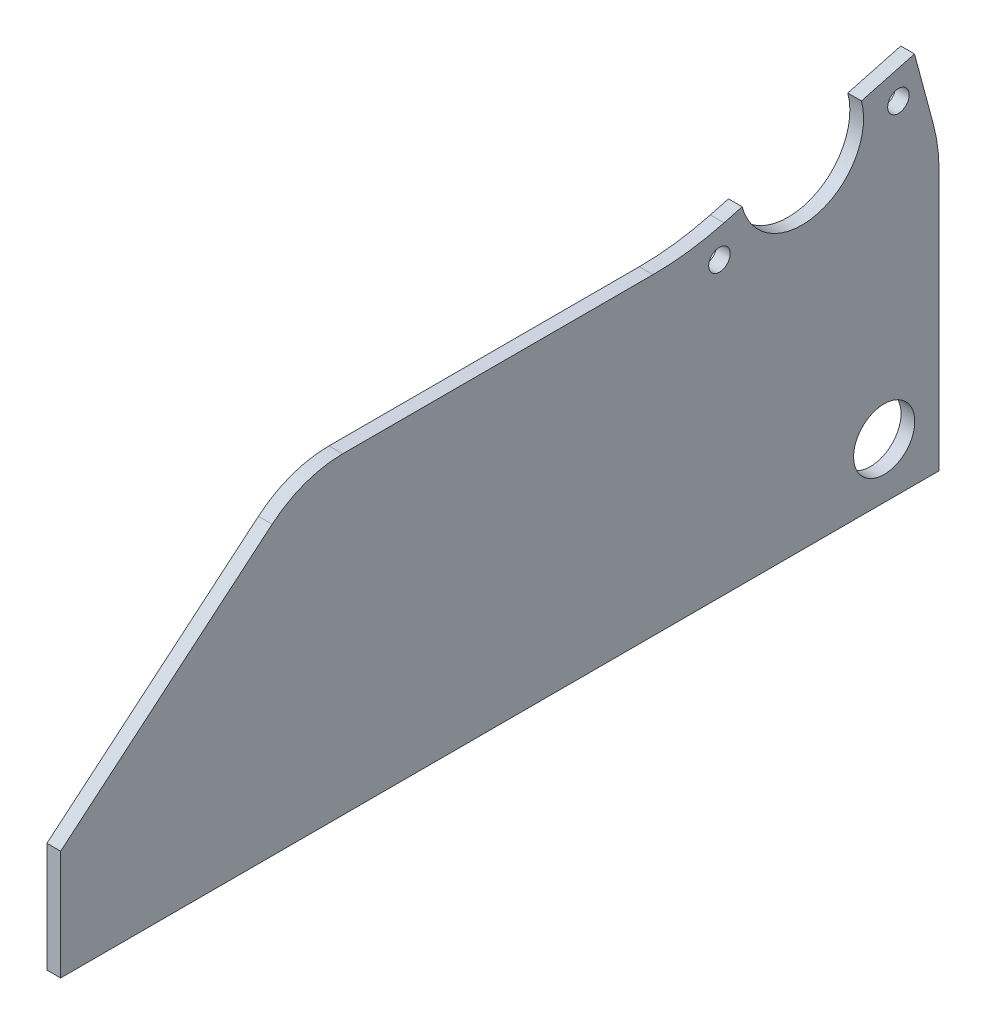
SolidWorks part; units mm, degrees
material "6061-T6 (SS)"
ref_plane "Front Plane" through (0, 0, 0) normal (0, 0, 1) x (1, 0, 0)
ref_plane "Top Plane" through (0, 0, 0) normal (0, 1, 0) x (1, 0, 0)
ref_plane "Right Plane" through (0, 0, 0) normal (1, 0, 0) x (0, 0, -1)
sketch "Sketch1" plane through (0, 0, 0) normal (1, 0, 0) x (0, 0, -1)
  line L0 (0, -25.4) -> (0, 39.7541)
  line L7 (-5.6821, 60.9599) -> (-17.9493, 57.6729)
  line L8 (-45.5507, 50.2771) -> (-57.8179, 46.9901)
  line L10 (-57.8179, 46.9901) -> (-137.9545, 46.9901)
  line L13 (-203.2, -25.4) -> (0, -25.4)
  line L14 (-203.2, -25.4) -> (-203.2, 0)
  line L15 (-203.2, 0) -> (-154.2813, 41.0476)
  line L16 (-203.2, 0) -> (0, 0) construction
  line L17 (-5.6821, 60.9599) -> (0, 39.7541)
  arc A2 (-17.9493, 57.6729) -> (-45.5507, 50.2771) centre (-31.75, 53.975) cw
  arc A4 (-137.9545, 46.9901) -> (-154.2813, 41.0476) centre (-137.9545, 21.5901) ccw
  circle A5 centre (-31.75, 53.975) radius 12.7 construction
  point P1 (0, 0)
  point P4 (0, 0)
  point P7 (-33.9318, 53.975)
  dimension "D1" = 28.575
  dimension "D4" = 25.4
  dimension "D7" = 25.4
  dimension "D10" = 25.4
  dimension "D3" = 41.275
  dimension "D11" = 15
  dimension "D9" = 31.75
  dimension "D2" = 15
  dimension "D5" = 12.7
  dimension "D6" = 203.2
  dimension "D8" = 50
extrude "Boss-Extrude1" add sketch "Sketch1" along normal blind 3.175
hole_wizard "#10 Clearance Hole1" positions "Sketch2" profile "Sketch3" hole size "#10" standard "ANSI Inch" end condition through all
sketch "Sketch2" plane through (3.175, 0, 0) normal (1, 0, 0) x (0, 0, -1)
  line L0 (-45.5507, 50.2771) -> (-57.8179, 46.9901) construction
  line L1 (-50.8075, 42.2946) -> (-9.4055, 53.3882) construction
  line L3 (-30.1065, 47.8414) -> (-31.75, 53.975) construction
  line L4 (-5.6821, 60.9599) -> (-17.9493, 57.6729) construction
  point P0 (-50.8075, 42.2946)
  point P2 (-9.4055, 53.3882)
  dimension "D1" = 42.8625
  dimension "D2" = 6.35
sketch "Sketch3" plane through (3.175, 42.2946, 50.8075) normal (0, 1, 0) x (0, 0, -1)
  line L0 (0, 0) -> (0, 3.175)
  line L1 (0, 3.175) -> (2.4892, 3.175)
  line L2 (2.4892, 3.175) -> (2.4892, 0)
  line L5 (2.4892, 0) -> (0, 0)
  line L11 (0, -6.35) -> (0, 107.95) construction
  dimension "Thru Hole Dia." = 4.9784
  dimension "Thru Hole Depth" = 3.175
sketch "Sketch9" plane through (3.175, 0, 0) normal (1, 0, 0) x (0, 0, -1)
  line L2 (0, -25.4) -> (0, 39.7541) construction
  line L3 (-203.2, -25.4) -> (0, -25.4) construction
  circle A0 centre (-12.7, -12.7) radius 7.0739
  dimension "D1" = 14.1478
  dimension "D3" = 12.7
  dimension "D2" = 12.7
extrude "Cut-Extrude1" cut sketch "Sketch9" against normal through all
fillet "Fillet1" radius 38.1 1 edges at (1.5875, 39.7541, 0)
fillet "Fillet2" radius 63.5 1 edges at (1.5875, 46.9901, 57.8179)
